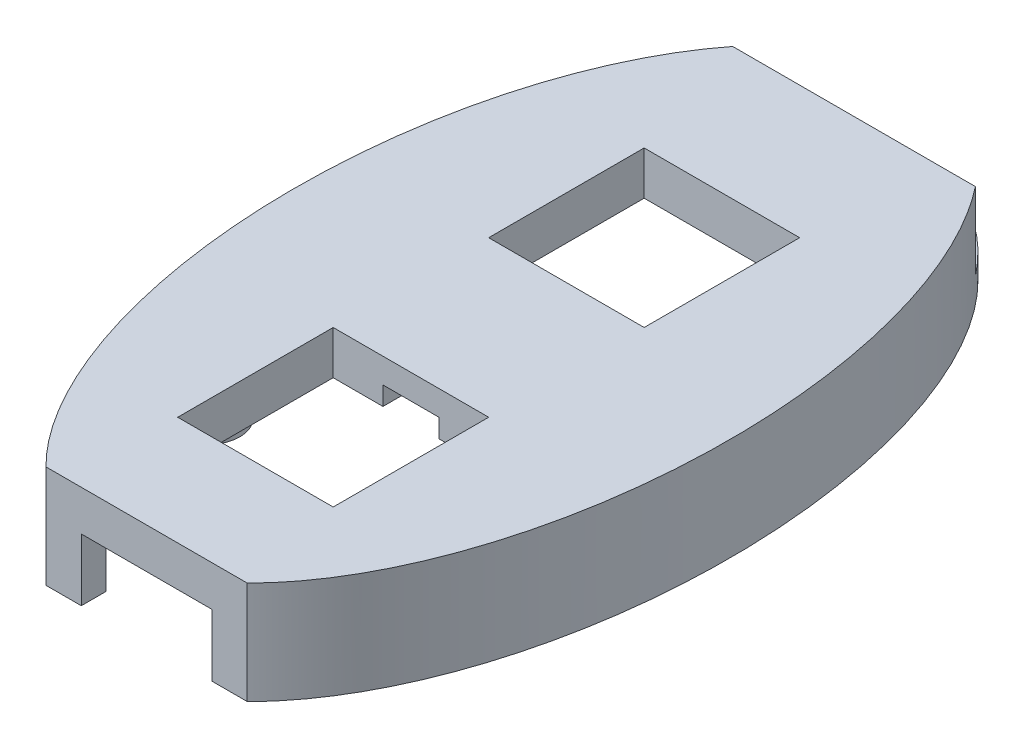
SolidWorks part; units mm, degrees
ref_plane "Front Plane" through (0, 0, 0) normal (0, 0, 1) x (1, 0, 0)
ref_plane "Top Plane" through (0, 0, 0) normal (0, 1, 0) x (1, 0, 0)
ref_plane "Right Plane" through (0, 0, 0) normal (1, 0, 0) x (0, 0, -1)
sketch "Sketch1" plane through (0, 0, 0) normal (0, 1, 0) x (1, 0, 0)
  line L0 (-8.2173, -29.845) -> (8.2173, -29.845)
  ellipse E0 centre (0, 0) end of major axis (0, -33.655) minor radius 17.78 (8.2173, -29.845) -> (-8.2173, -29.845) ccw
  dimension "D1" = 67.31
  dimension "D2" = 35.56
  dimension "D3" = 63.5
extrude "Boss-Extrude1" add sketch "Sketch1" against normal blind 2.032
sketch "Sketch17" plane through (0, 0, 0) normal (0, 1, 0) x (1, 0, 0)
  line L0 (0, 0) -> (0, 50.5429) construction
  line L1 (-6.35, 17.145) -> (6.35, 17.145)
  line L2 (-6.35, 17.145) -> (-6.35, 4.445)
  line L3 (-6.35, 4.445) -> (6.35, 4.445)
  line L4 (6.35, 17.145) -> (6.35, 4.445)
  line L5 (-6.35, 17.145) -> (6.35, 4.445) construction
  line L6 (-6.35, 4.445) -> (6.35, 17.145) construction
  line L7 (-6.35, -8.255) -> (6.35, -8.255)
  line L8 (-6.35, -8.255) -> (-6.35, -20.955)
  line L9 (-6.35, -20.955) -> (6.35, -20.955)
  line L10 (6.35, -8.255) -> (6.35, -20.955)
  line L11 (-6.35, -8.255) -> (6.35, -20.955) construction
  line L12 (-6.35, -20.955) -> (6.35, -8.255) construction
  line L13 (-8.2173, -29.845) -> (8.2173, -29.845) construction
  point P0 (0, 10.795)
  point P5 (0, -14.605)
  dimension "D1" = 12.7
  dimension "D2" = 15.24
  dimension "D3" = 40.64
extrude "Cut-Extrude13" cut sketch "Sketch17" against normal through all
sketch "Sketch18" plane through (0, -2.032, 0) normal (0, 1, 0) x (1, 0, 0)
  line L105 (-8.382, 19.177) -> (-8.382, 2.413)
  line L106 (-8.382, 2.413) -> (8.382, 2.413)
  line L107 (8.382, 2.413) -> (8.382, 19.177)
  line L108 (8.382, 19.177) -> (-8.382, 19.177)
  line L109 (-8.382, 19.177) -> (-8.382, 2.413)
  line L110 (-8.382, 2.413) -> (-2.286, 2.413)
  line L111 (8.382, 2.413) -> (8.382, 19.177)
  line L112 (8.382, 19.177) -> (-8.382, 19.177)
  line L113 (-6.35, 17.145) -> (-6.35, 4.445) construction
  line L114 (6.35, 17.145) -> (-6.35, 17.145) construction
  line L115 (-6.35, 4.445) -> (6.35, 4.445) construction
  line L116 (6.35, 4.445) -> (6.35, 17.145) construction
  line L117 (8.382, -22.987) -> (8.382, -6.223)
  line L118 (8.382, -6.223) -> (-8.382, -6.223)
  line L119 (-8.382, -6.223) -> (-8.382, -22.987)
  line L120 (-8.382, -22.987) -> (8.382, -22.987)
  line L121 (8.382, -22.987) -> (8.382, -6.223)
  line L122 (8.382, -6.223) -> (2.286, -6.223)
  line L123 (-8.382, -6.223) -> (-8.382, -22.987)
  line L124 (-8.382, -22.987) -> (8.382, -22.987)
  line L125 (-6.35, 17.145) -> (-6.35, 4.445)
  line L126 (6.35, 17.145) -> (-6.35, 17.145)
  line L127 (-6.35, 4.445) -> (-2.286, 4.445)
  line L128 (6.35, 4.445) -> (6.35, 17.145)
  line L129 (6.35, -8.255) -> (-6.35, -8.255) construction
  line L130 (6.35, -20.955) -> (6.35, -8.255) construction
  line L131 (-6.35, -20.955) -> (6.35, -20.955) construction
  line L132 (-6.35, -8.255) -> (-6.35, -20.955) construction
  line L133 (6.35, -8.255) -> (2.286, -8.255)
  line L134 (6.35, -20.955) -> (6.35, -8.255)
  line L135 (-6.35, -20.955) -> (6.35, -20.955)
  line L136 (-6.35, -8.255) -> (-6.35, -20.955)
  line L137 (-2.286, -8.255) -> (-2.286, -6.223)
  line L139 (2.286, 4.445) -> (2.286, 2.413)
  line L141 (0, 0) -> (0, 31.2149) construction
  line L142 (2.286, 2.413) -> (8.382, 2.413)
  line L143 (2.286, 4.445) -> (6.35, 4.445)
  line L144 (-2.286, -6.223) -> (-8.382, -6.223)
  line L145 (-2.286, -8.255) -> (-6.35, -8.255)
  line L146 (-2.286, 2.413) -> (-2.286, 4.445)
  line L147 (2.286, -6.223) -> (2.286, -8.255)
  dimension "D3" = 4.572
  dimension "D1" = 2.032
  dimension "D2" = 2.032
extrude "LightBox" add sketch "Sketch18" against normal blind 1.524
sketch "Sketch19" plane through (0, -2.032, 0) normal (0, -1, 0) x (1, 0, 0)
  line L0 (0, 0) -> (0, 18.966) construction
  circle A0 centre (-13.462, 11.43) radius 1.1303
  circle A1 centre (13.462, 11.43) radius 1.1303
  circle A2 centre (13.462, 11.43) radius 2.6543
  circle A3 centre (-13.462, 11.43) radius 2.6543
  point P9 (11.6395, 12.7358)
  dimension "D3" = 2.2606
  dimension "D1" = 11.43
  dimension "D2" = 26.924
  dimension "D4" = 1.524
extrude "Boss-Screws" add sketch "Sketch19" along normal blind 6.35
sketch "Sketch20" plane through (0, -2.032, 0) normal (0, -1, 0) x (1, 0, 0)
  line L0 (-8.2173, 29.845) -> (8.2173, 29.845) construction
  line L1 (-8.2173, 29.845) -> (8.2173, 29.845)
  line L2 (-7.3554, 27.813) -> (7.3554, 27.813)
  ellipse E0 centre (0, 0) end of major axis (0, 33.655) minor radius 17.78 (-8.2173, 29.845) -> (8.2173, 29.845) ccw construction
  ellipse E1 centre (0, 0) end of major axis (0, 33.655) minor radius 17.78 (-8.2173, 29.845) -> (8.2173, 29.845) ccw
  spline S0 degree 1 poles (-7.3554, 27.813) (7.3554, 27.813) knots 0 0 1 1 construction
  spline S1 degree 3 poles (-7.3554, 27.813) (-7.747, 27.3876) (-8.4711, 26.523) (-9.5515, 24.9917) (-10.5644, 23.2899) (-11.8281, 20.7908) (-13.2119, 17.2782) (-14.4988, 12.5627) (-15.3664, 7.4855) (-15.9268, 0.4294) (-15.4665, -8.5478) (-13.1226, -18.3463) (-9.3021, -26.0406) (-5.4001, -29.9288) (-2.2834, -31.3895) (0, -31.7398) (2.2834, -31.3895) (5.4001, -29.9288) (9.3021, -26.0406) (13.1226, -18.3463) (15.4665, -8.5478) (15.9268, 0.4294) (15.3664, 7.4855) (14.4988, 12.5627) (13.2119, 17.2782) (11.8281, 20.7908) (10.5644, 23.2899) (9.5515, 24.9917) (8.4711, 26.523) (7.747, 27.3876) (7.3554, 27.813) knots 0.521032 0.521032 0.521032 0.521032 0.602925 0.684817 0.76671 0.848602 1.012387 1.176172 1.339957 1.503742 1.831312 2.158882 2.486453 2.814023 2.977808 3.141593 3.305378 3.469163 3.796733 4.124303 4.451873 4.779443 4.943228 5.107013 5.270798 5.434583 5.516476 5.598368 5.680261 5.762153 5.762153 5.762153 5.762153
  dimension "D1" = 2.032
extrude "FlangeOuter" add sketch "Sketch20" along normal blind 6.35
sketch "Sketch21" plane through (0, 0, 29.845) normal (0, 0, 1) x (1, 0, 0)
  line L0 (8.2173, -8.382) -> (-8.2173, -8.382) construction
  line L1 (-5.334, -8.382) -> (5.334, -8.382)
  line L2 (-5.334, -8.382) -> (-5.334, -3.302)
  line L3 (-5.334, -3.302) -> (5.334, -3.302)
  line L4 (5.334, -8.382) -> (5.334, -3.302)
  line L5 (0, 0) -> (0, -14.4473) construction
  line L6 (-8.2173, 0) -> (8.2173, 0) construction
  dimension "D1" = 5.08
  dimension "D2" = 10.668
extrude "Cut-Extrude14" cut sketch "Sketch21" against normal up to next
sketch "Sketch22" plane through (0, 0, 0) normal (0, 1, 0) x (1, 0, 0)
  line L0 (0, 0) -> (0, 47.2593) construction
  line L1 (-25.4, 53.34) -> (25.4, 53.34)
  line L2 (-25.4, 53.34) -> (-25.4, 27.94)
  line L3 (-25.4, 27.94) -> (25.4, 27.94)
  line L4 (25.4, 53.34) -> (25.4, 27.94)
  dimension "D1" = 27.94
  dimension "D2" = 25.4
  dimension "D3" = 50.8
extrude "Cut-Extrude15" cut sketch "Sketch22" against normal offset from surface (6.35 mm away) 2.032 up to face at (-0.693, -8.382, 17.6865)
sketch "Sketch25" plane through (0, -6.35, 0) normal (0, 1, 0) x (1, 0, 0)
  line L0 (-9.2845, 28.702) -> (9.2845, 28.702)
  line L1 (-9.912, 27.94) -> (9.912, 27.94) construction
  ellipse E0 centre (0, 0) end of major axis (0, -33.655) minor radius 17.78 (9.912, 27.94) -> (-9.912, 27.94) ccw construction
  ellipse E1 centre (0, 0) end of major axis (0, -33.655) minor radius 17.78 (9.2845, 28.702) -> (-9.2845, 28.702) ccw
  dimension "D1" = 0.762
extrude "Boss-Extrude8" add sketch "Sketch25" against normal through all
